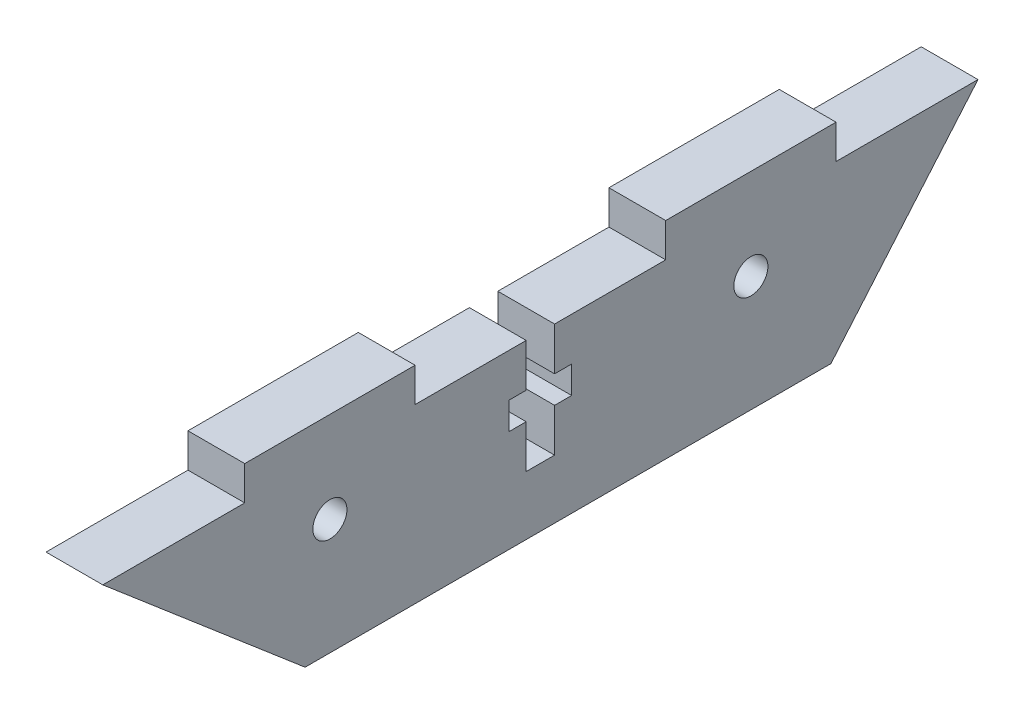
SolidWorks part; units mm, degrees
material "PMMA"
ref_plane "Front Plane" through (0, 0, 0) normal (0, 0, 1) x (1, 0, 0)
ref_plane "Top Plane" through (0, 0, 0) normal (0, 1, 0) x (1, 0, 0)
ref_plane "Right Plane" through (0, 0, 0) normal (1, 0, 0) x (0, 0, -1)
sketch "Schizzo1" plane through (0, 0, 0) normal (1, 0, 0) x (0, 0, -1)
  line L0 (-38.535, -7.595) -> (38.535, 7.595) construction
  line L1 (-38.535, 7.595) -> (38.535, 7.595)
  line L2 (-38.535, 7.595) -> (-38.535, -7.595)
  line L3 (-38.535, -7.595) -> (38.535, -7.595)
  line L4 (38.535, 7.595) -> (38.535, -7.595)
  point P4 (0, 0)
  dimension "D1" = 15.19
  dimension "D2" = 77.07
extrude "Estrusione-Estrusione1" add sketch "Schizzo1" along normal blind 5
sketch "Schizzo3" plane through (0, 0, 0) normal (1, 0, 0) x (0, 0, -1)
  line L0 (-38.535, 7.595) -> (-38.535, -7.595) construction
  line L1 (38.535, 7.595) -> (-38.535, 7.595) construction
  line L2 (38.535, -7.595) -> (38.535, 7.595) construction
  circle A0 centre (-18.535, 2.595) radius 1.5
  circle A1 centre (18.535, 2.595) radius 1.5
  dimension "D1" = 3
  dimension "D2" = 20
  dimension "D3" = 5
  dimension "D4" = 20
  dimension "D5" = 5
sketch "Schizzo2" plane through (0, 0, 0) normal (1, 0, 0) x (0, 0, -1)
  line L0 (38.535, 7.595) -> (25.5844, -7.595)
  line L1 (-38.535, -7.595) -> (38.535, -7.595) construction
  line L2 (25.5844, -7.595) -> (38.535, -7.595)
  line L3 (38.535, -7.595) -> (38.535, 7.595)
  line L4 (-38.535, 7.595) -> (-38.535, -7.595)
  line L5 (-38.535, -7.595) -> (-20.7183, -7.595)
  line L6 (-20.7183, -7.595) -> (-38.535, 7.595)
  line L7 (38.535, 7.595) -> (-38.535, 7.595) construction
  dimension "D1" = 49.55
  dimension "D2" = 40.45
extrude "Taglio-Estrusione1" cut sketch "Schizzo2" along direction (1, 0, 0) on the side of the normal through all
extrude "Taglio-Estrusione2" cut sketch "Schizzo3" along direction (1, 0, 0) on the side of the normal through all
sketch "Schizzo4" plane through (0, 7.595, 0) normal (0, 1, 0) x (1, 0, 0)
  line L0 (5, 18.535) -> (0, 18.535) construction
  line L1 (5, 38.535) -> (5, -38.535) construction
  line L2 (0, 38.535) -> (0, -38.535) construction
  line L4 (5, 38.535) -> (0, 38.535) construction
  line L6 (5, 0) -> (0, 0) construction
  line L7 (0, 26.035) -> (5, 26.035)
  line L8 (0, 26.035) -> (0, 11.035)
  line L9 (0, 11.035) -> (5, 11.035)
  line L10 (5, 26.035) -> (5, 11.035)
  line L11 (0, -26.035) -> (0, -11.035)
  line L12 (0, -26.035) -> (5, -26.035)
  line L13 (5, -26.035) -> (5, -11.035)
  line L14 (0, -11.035) -> (5, -11.035)
  point P16 (5, 18.535)
  dimension "D1" = 20
  dimension "D2" = 12.5
  dimension "D3" = 15
extrude "Estrusione-Estrusione2" add sketch "Schizzo4" along normal blind 3
sketch "Schizzo6" plane through (0, 0, 0) normal (1, 0, 0) x (0, 0, -1)
  line L0 (0, -2.405) -> (0, 7.595) construction
  line L1 (-1.25, -2.405) -> (-1.25, 1.395)
  line L2 (-1.25, 1.395) -> (-2.75, 1.395)
  line L3 (-2.75, 1.395) -> (-2.75, 3.795)
  line L4 (-2.75, 3.795) -> (-1.25, 3.795)
  line L5 (-1.25, 3.795) -> (-1.25, 7.595)
  line L6 (-1.25, 7.595) -> (1.25, 7.595)
  line L7 (1.25, 7.595) -> (1.25, 3.795)
  line L8 (1.25, 3.795) -> (2.75, 3.795)
  line L9 (2.75, 3.795) -> (2.75, 1.395)
  line L10 (2.75, 1.395) -> (1.25, 1.395)
  line L11 (1.25, 1.395) -> (1.25, -2.405)
  line L12 (1.25, -2.405) -> (-1.25, -2.405)
  line L13 (0, 7.595) -> (0, -7.595) construction
  line L14 (11.035, 7.595) -> (-11.035, 7.595) construction
  line L15 (-20.7183, -7.595) -> (25.5844, -7.595) construction
  point P14 (0, -2.405)
  dimension "D1" = 2.4
  dimension "D2" = 10
  dimension "D3" = 90
  dimension "D4" = 90
  dimension "D5" = 2.5
  dimension "D6" = 5.5
extrude "Taglio-Estrusione3" cut sketch "Schizzo6" along normal through all
equation "\"Thickness5\"= 5"
equation "\"D1@Estrusione-Estrusione1\"=\"Thickness5\""
equation "\"D1@Estrusione-Estrusione2\"=\"Thickness3\""
equation "\"Thickness3\"= 3"
